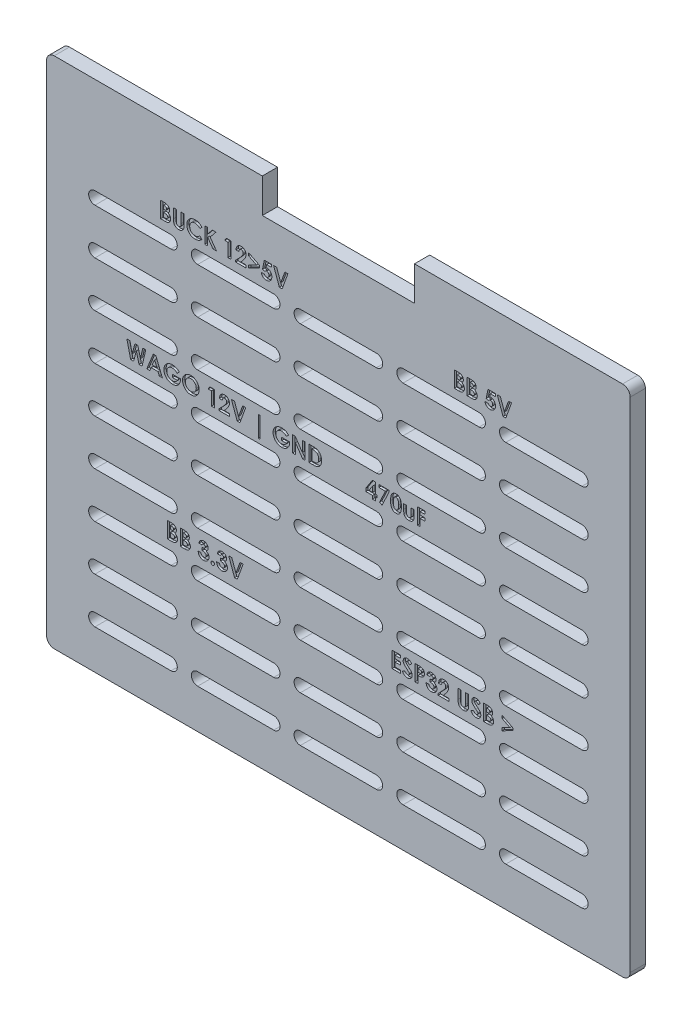
SolidWorks part; units mm, degrees
ref_plane "Front Plane" through (0, 0, 0) normal (0, 0, 1) x (1, 0, 0)
ref_plane "Top Plane" through (0, 0, 0) normal (0, 1, 0) x (1, 0, 0)
ref_plane "Right Plane" through (0, 0, 0) normal (1, 0, 0) x (0, 0, -1)
ref_plane "P1_Front_14" through (0, 0, 14) normal (0, 0, 1) x (1, 0, 0)
sketch "Sketch1" plane through (0, 0, 14) normal (0, 0, 1) x (1, 0, 0)
  line L0 (-74.7, 9) -> (74.7, 9)
  line L1 (76.7, 11) -> (76.7, 142)
  line L2 (74.7, 144) -> (-74.7, 144)
  line L3 (-76.7, 142) -> (-76.7, 11)
  arc A0 (-76.7, 11) -> (-74.7, 9) centre (-74.7, 11) ccw
  arc A1 (74.7, 9) -> (76.7, 11) centre (74.7, 11) ccw
  arc A2 (76.7, 142) -> (74.7, 144) centre (74.7, 142) ccw
  arc A3 (-74.7, 144) -> (-76.7, 142) centre (-74.7, 142) ccw
extrude "Plate" add sketch "Sketch1" along normal blind 4
sketch "Sketch2" plane through (0, 0, 14) normal (0, 0, 1) x (1, 0, 0)
  line L0 (-64, 21) -> (-44, 21) construction
  line L1 (-20, 135) -> (20, 135)
  line L2 (-20, 135) -> (-20, 144)
  line L3 (-20, 144) -> (20, 144)
  line L4 (20, 135) -> (20, 144)
  line L5 (-20, 135) -> (20, 144) construction
  line L6 (-20, 144) -> (20, 135) construction
  line L7 (-64, 22.65) -> (-44, 22.65)
  line L8 (-64, 19.35) -> (-44, 19.35)
  line L9 (-37, 21) -> (-17, 21) construction
  line L10 (-37, 22.65) -> (-17, 22.65)
  line L11 (-37, 19.35) -> (-17, 19.35)
  line L12 (-10, 21) -> (10, 21) construction
  line L13 (-10, 22.65) -> (10, 22.65)
  line L14 (-10, 19.35) -> (10, 19.35)
  line L15 (17, 21) -> (37, 21) construction
  line L16 (17, 22.65) -> (37, 22.65)
  line L17 (17, 19.35) -> (37, 19.35)
  line L18 (44, 21) -> (64, 21) construction
  line L19 (44, 22.65) -> (64, 22.65)
  line L20 (44, 19.35) -> (64, 19.35)
  line L21 (-64, 33) -> (-44, 33) construction
  line L22 (-64, 34.65) -> (-44, 34.65)
  line L23 (-64, 31.35) -> (-44, 31.35)
  line L24 (-37, 33) -> (-17, 33) construction
  line L25 (-37, 34.65) -> (-17, 34.65)
  line L26 (-37, 31.35) -> (-17, 31.35)
  line L27 (-10, 33) -> (10, 33) construction
  line L28 (-10, 34.65) -> (10, 34.65)
  line L29 (-10, 31.35) -> (10, 31.35)
  line L30 (17, 33) -> (37, 33) construction
  line L31 (17, 34.65) -> (37, 34.65)
  line L32 (17, 31.35) -> (37, 31.35)
  line L33 (44, 33) -> (64, 33) construction
  line L34 (44, 34.65) -> (64, 34.65)
  line L35 (44, 31.35) -> (64, 31.35)
  line L36 (-64, 45) -> (-44, 45) construction
  line L37 (-64, 46.65) -> (-44, 46.65)
  line L38 (-64, 43.35) -> (-44, 43.35)
  line L39 (-37, 45) -> (-17, 45) construction
  line L40 (-37, 46.65) -> (-17, 46.65)
  line L41 (-37, 43.35) -> (-17, 43.35)
  line L42 (-10, 45) -> (10, 45) construction
  line L43 (-10, 46.65) -> (10, 46.65)
  line L44 (-10, 43.35) -> (10, 43.35)
  line L45 (17, 45) -> (37, 45) construction
  line L46 (17, 46.65) -> (37, 46.65)
  line L47 (17, 43.35) -> (37, 43.35)
  line L48 (44, 45) -> (64, 45) construction
  line L49 (44, 46.65) -> (64, 46.65)
  line L50 (44, 43.35) -> (64, 43.35)
  line L51 (-64, 57) -> (-44, 57) construction
  line L52 (-64, 58.65) -> (-44, 58.65)
  line L53 (-64, 55.35) -> (-44, 55.35)
  line L54 (-37, 57) -> (-17, 57) construction
  line L55 (-37, 58.65) -> (-17, 58.65)
  line L56 (-37, 55.35) -> (-17, 55.35)
  line L57 (-10, 57) -> (10, 57) construction
  line L58 (-10, 58.65) -> (10, 58.65)
  line L59 (-10, 55.35) -> (10, 55.35)
  line L60 (17, 57) -> (37, 57) construction
  line L61 (17, 58.65) -> (37, 58.65)
  line L62 (17, 55.35) -> (37, 55.35)
  line L63 (44, 57) -> (64, 57) construction
  line L64 (44, 58.65) -> (64, 58.65)
  line L65 (44, 55.35) -> (64, 55.35)
  line L66 (-64, 69) -> (-44, 69) construction
  line L67 (-64, 70.65) -> (-44, 70.65)
  line L68 (-64, 67.35) -> (-44, 67.35)
  line L69 (-37, 69) -> (-17, 69) construction
  line L70 (-37, 70.65) -> (-17, 70.65)
  line L71 (-37, 67.35) -> (-17, 67.35)
  line L72 (-10, 69) -> (10, 69) construction
  line L73 (-10, 70.65) -> (10, 70.65)
  line L74 (-10, 67.35) -> (10, 67.35)
  line L75 (17, 69) -> (37, 69) construction
  line L76 (17, 70.65) -> (37, 70.65)
  line L77 (17, 67.35) -> (37, 67.35)
  line L78 (44, 69) -> (64, 69) construction
  line L79 (44, 70.65) -> (64, 70.65)
  line L80 (44, 67.35) -> (64, 67.35)
  line L81 (-64, 81) -> (-44, 81) construction
  line L82 (-64, 82.65) -> (-44, 82.65)
  line L83 (-64, 79.35) -> (-44, 79.35)
  line L84 (-37, 81) -> (-17, 81) construction
  line L85 (-37, 82.65) -> (-17, 82.65)
  line L86 (-37, 79.35) -> (-17, 79.35)
  line L87 (-10, 81) -> (10, 81) construction
  line L88 (-10, 82.65) -> (10, 82.65)
  line L89 (-10, 79.35) -> (10, 79.35)
  line L90 (17, 81) -> (37, 81) construction
  line L91 (17, 82.65) -> (37, 82.65)
  line L92 (17, 79.35) -> (37, 79.35)
  line L93 (44, 81) -> (64, 81) construction
  line L94 (44, 82.65) -> (64, 82.65)
  line L95 (44, 79.35) -> (64, 79.35)
  line L96 (-64, 93) -> (-44, 93) construction
  line L97 (-64, 94.65) -> (-44, 94.65)
  line L98 (-64, 91.35) -> (-44, 91.35)
  line L99 (-37, 93) -> (-17, 93) construction
  line L100 (-37, 94.65) -> (-17, 94.65)
  line L101 (-37, 91.35) -> (-17, 91.35)
  line L102 (-10, 93) -> (10, 93) construction
  line L103 (-10, 94.65) -> (10, 94.65)
  line L104 (-10, 91.35) -> (10, 91.35)
  line L105 (17, 93) -> (37, 93) construction
  line L106 (17, 94.65) -> (37, 94.65)
  line L107 (17, 91.35) -> (37, 91.35)
  line L108 (44, 93) -> (64, 93) construction
  line L109 (44, 94.65) -> (64, 94.65)
  line L110 (44, 91.35) -> (64, 91.35)
  line L111 (-64, 105) -> (-44, 105) construction
  line L112 (-64, 106.65) -> (-44, 106.65)
  line L113 (-64, 103.35) -> (-44, 103.35)
  line L114 (-37, 105) -> (-17, 105) construction
  line L115 (-37, 106.65) -> (-17, 106.65)
  line L116 (-37, 103.35) -> (-17, 103.35)
  line L117 (-10, 105) -> (10, 105) construction
  line L118 (-10, 106.65) -> (10, 106.65)
  line L119 (-10, 103.35) -> (10, 103.35)
  line L120 (17, 105) -> (37, 105) construction
  line L121 (17, 106.65) -> (37, 106.65)
  line L122 (17, 103.35) -> (37, 103.35)
  line L123 (44, 105) -> (64, 105) construction
  line L124 (44, 106.65) -> (64, 106.65)
  line L125 (44, 103.35) -> (64, 103.35)
  line L126 (-64, 117) -> (-44, 117) construction
  line L127 (-64, 118.65) -> (-44, 118.65)
  line L128 (-64, 115.35) -> (-44, 115.35)
  line L129 (-37, 117) -> (-17, 117) construction
  line L130 (-37, 118.65) -> (-17, 118.65)
  line L131 (-37, 115.35) -> (-17, 115.35)
  line L132 (-10, 117) -> (10, 117) construction
  line L133 (-10, 118.65) -> (10, 118.65)
  line L134 (-10, 115.35) -> (10, 115.35)
  line L135 (17, 117) -> (37, 117) construction
  line L136 (17, 118.65) -> (37, 118.65)
  line L137 (17, 115.35) -> (37, 115.35)
  line L138 (44, 117) -> (64, 117) construction
  line L139 (44, 118.65) -> (64, 118.65)
  line L140 (44, 115.35) -> (64, 115.35)
  arc A0 (-64, 22.65) -> (-64, 19.35) centre (-64, 21) ccw
  arc A1 (-44, 19.35) -> (-44, 22.65) centre (-44, 21) ccw
  arc A2 (-37, 22.65) -> (-37, 19.35) centre (-37, 21) ccw
  arc A3 (-17, 19.35) -> (-17, 22.65) centre (-17, 21) ccw
  arc A4 (-10, 22.65) -> (-10, 19.35) centre (-10, 21) ccw
  arc A5 (10, 19.35) -> (10, 22.65) centre (10, 21) ccw
  arc A6 (17, 22.65) -> (17, 19.35) centre (17, 21) ccw
  arc A7 (37, 19.35) -> (37, 22.65) centre (37, 21) ccw
  arc A8 (44, 22.65) -> (44, 19.35) centre (44, 21) ccw
  arc A9 (64, 19.35) -> (64, 22.65) centre (64, 21) ccw
  arc A10 (-64, 34.65) -> (-64, 31.35) centre (-64, 33) ccw
  arc A11 (-44, 31.35) -> (-44, 34.65) centre (-44, 33) ccw
  arc A12 (-37, 34.65) -> (-37, 31.35) centre (-37, 33) ccw
  arc A13 (-17, 31.35) -> (-17, 34.65) centre (-17, 33) ccw
  arc A14 (-10, 34.65) -> (-10, 31.35) centre (-10, 33) ccw
  arc A15 (10, 31.35) -> (10, 34.65) centre (10, 33) ccw
  arc A16 (17, 34.65) -> (17, 31.35) centre (17, 33) ccw
  arc A17 (37, 31.35) -> (37, 34.65) centre (37, 33) ccw
  arc A18 (44, 34.65) -> (44, 31.35) centre (44, 33) ccw
  arc A19 (64, 31.35) -> (64, 34.65) centre (64, 33) ccw
  arc A20 (-64, 46.65) -> (-64, 43.35) centre (-64, 45) ccw
  arc A21 (-44, 43.35) -> (-44, 46.65) centre (-44, 45) ccw
  arc A22 (-37, 46.65) -> (-37, 43.35) centre (-37, 45) ccw
  arc A23 (-17, 43.35) -> (-17, 46.65) centre (-17, 45) ccw
  arc A24 (-10, 46.65) -> (-10, 43.35) centre (-10, 45) ccw
  arc A25 (10, 43.35) -> (10, 46.65) centre (10, 45) ccw
  arc A26 (17, 46.65) -> (17, 43.35) centre (17, 45) ccw
  arc A27 (37, 43.35) -> (37, 46.65) centre (37, 45) ccw
  arc A28 (44, 46.65) -> (44, 43.35) centre (44, 45) ccw
  arc A29 (64, 43.35) -> (64, 46.65) centre (64, 45) ccw
  arc A30 (-64, 58.65) -> (-64, 55.35) centre (-64, 57) ccw
  arc A31 (-44, 55.35) -> (-44, 58.65) centre (-44, 57) ccw
  arc A32 (-37, 58.65) -> (-37, 55.35) centre (-37, 57) ccw
  arc A33 (-17, 55.35) -> (-17, 58.65) centre (-17, 57) ccw
  arc A34 (-10, 58.65) -> (-10, 55.35) centre (-10, 57) ccw
  arc A35 (10, 55.35) -> (10, 58.65) centre (10, 57) ccw
  arc A36 (17, 58.65) -> (17, 55.35) centre (17, 57) ccw
  arc A37 (37, 55.35) -> (37, 58.65) centre (37, 57) ccw
  arc A38 (44, 58.65) -> (44, 55.35) centre (44, 57) ccw
  arc A39 (64, 55.35) -> (64, 58.65) centre (64, 57) ccw
  arc A40 (-64, 70.65) -> (-64, 67.35) centre (-64, 69) ccw
  arc A41 (-44, 67.35) -> (-44, 70.65) centre (-44, 69) ccw
  arc A42 (-37, 70.65) -> (-37, 67.35) centre (-37, 69) ccw
  arc A43 (-17, 67.35) -> (-17, 70.65) centre (-17, 69) ccw
  arc A44 (-10, 70.65) -> (-10, 67.35) centre (-10, 69) ccw
  arc A45 (10, 67.35) -> (10, 70.65) centre (10, 69) ccw
  arc A46 (17, 70.65) -> (17, 67.35) centre (17, 69) ccw
  arc A47 (37, 67.35) -> (37, 70.65) centre (37, 69) ccw
  arc A48 (44, 70.65) -> (44, 67.35) centre (44, 69) ccw
  arc A49 (64, 67.35) -> (64, 70.65) centre (64, 69) ccw
  arc A50 (-64, 82.65) -> (-64, 79.35) centre (-64, 81) ccw
  arc A51 (-44, 79.35) -> (-44, 82.65) centre (-44, 81) ccw
  arc A52 (-37, 82.65) -> (-37, 79.35) centre (-37, 81) ccw
  arc A53 (-17, 79.35) -> (-17, 82.65) centre (-17, 81) ccw
  arc A54 (-10, 82.65) -> (-10, 79.35) centre (-10, 81) ccw
  arc A55 (10, 79.35) -> (10, 82.65) centre (10, 81) ccw
  arc A56 (17, 82.65) -> (17, 79.35) centre (17, 81) ccw
  arc A57 (37, 79.35) -> (37, 82.65) centre (37, 81) ccw
  arc A58 (44, 82.65) -> (44, 79.35) centre (44, 81) ccw
  arc A59 (64, 79.35) -> (64, 82.65) centre (64, 81) ccw
  arc A60 (-64, 94.65) -> (-64, 91.35) centre (-64, 93) ccw
  arc A61 (-44, 91.35) -> (-44, 94.65) centre (-44, 93) ccw
  arc A62 (-37, 94.65) -> (-37, 91.35) centre (-37, 93) ccw
  arc A63 (-17, 91.35) -> (-17, 94.65) centre (-17, 93) ccw
  arc A64 (-10, 94.65) -> (-10, 91.35) centre (-10, 93) ccw
  arc A65 (10, 91.35) -> (10, 94.65) centre (10, 93) ccw
  arc A66 (17, 94.65) -> (17, 91.35) centre (17, 93) ccw
  arc A67 (37, 91.35) -> (37, 94.65) centre (37, 93) ccw
  arc A68 (44, 94.65) -> (44, 91.35) centre (44, 93) ccw
  arc A69 (64, 91.35) -> (64, 94.65) centre (64, 93) ccw
  arc A70 (-64, 106.65) -> (-64, 103.35) centre (-64, 105) ccw
  arc A71 (-44, 103.35) -> (-44, 106.65) centre (-44, 105) ccw
  arc A72 (-37, 106.65) -> (-37, 103.35) centre (-37, 105) ccw
  arc A73 (-17, 103.35) -> (-17, 106.65) centre (-17, 105) ccw
  arc A74 (-10, 106.65) -> (-10, 103.35) centre (-10, 105) ccw
  arc A75 (10, 103.35) -> (10, 106.65) centre (10, 105) ccw
  arc A76 (17, 106.65) -> (17, 103.35) centre (17, 105) ccw
  arc A77 (37, 103.35) -> (37, 106.65) centre (37, 105) ccw
  arc A78 (44, 106.65) -> (44, 103.35) centre (44, 105) ccw
  arc A79 (64, 103.35) -> (64, 106.65) centre (64, 105) ccw
  arc A80 (-64, 118.65) -> (-64, 115.35) centre (-64, 117) ccw
  arc A81 (-44, 115.35) -> (-44, 118.65) centre (-44, 117) ccw
  arc A82 (-37, 118.65) -> (-37, 115.35) centre (-37, 117) ccw
  arc A83 (-17, 115.35) -> (-17, 118.65) centre (-17, 117) ccw
  arc A84 (-10, 118.65) -> (-10, 115.35) centre (-10, 117) ccw
  arc A85 (10, 115.35) -> (10, 118.65) centre (10, 117) ccw
  arc A86 (17, 118.65) -> (17, 115.35) centre (17, 117) ccw
  arc A87 (37, 115.35) -> (37, 118.65) centre (37, 117) ccw
  arc A88 (44, 118.65) -> (44, 115.35) centre (44, 117) ccw
  arc A89 (64, 115.35) -> (64, 118.65) centre (64, 117) ccw
  point P0 (0, 139.5)
  point P7 (-54, 21)
  point P12 (-27, 21)
  point P19 (0, 21)
  point P26 (27, 21)
  point P33 (54, 21)
  point P40 (-54, 33)
  point P47 (-27, 33)
  point P54 (0, 33)
  point P61 (27, 33)
  point P68 (54, 33)
  point P75 (-54, 45)
  point P82 (-27, 45)
  point P89 (0, 45)
  point P96 (27, 45)
  point P103 (54, 45)
  point P110 (-54, 57)
  point P117 (-27, 57)
  point P124 (0, 57)
  point P131 (27, 57)
  point P138 (54, 57)
  point P145 (-54, 69)
  point P152 (-27, 69)
  point P159 (0, 69)
  point P166 (27, 69)
  point P173 (54, 69)
  point P180 (-54, 81)
  point P187 (-27, 81)
  point P194 (0, 81)
  point P201 (27, 81)
  point P208 (54, 81)
  point P215 (-54, 93)
  point P222 (-27, 93)
  point P229 (0, 93)
  point P236 (27, 93)
  point P243 (54, 93)
  point P250 (-54, 105)
  point P257 (-27, 105)
  point P264 (0, 105)
  point P271 (27, 105)
  point P278 (54, 105)
  point P285 (-54, 117)
  point P292 (-27, 117)
  point P299 (0, 117)
  point P306 (27, 117)
  point P313 (54, 117)
  point P320 (0, 0)
extrude "Notch and mounting slots" cut sketch "Sketch2" along normal through all
ref_plane "P2_Front_18" through (0, 0, 18) normal (0, 0, 1) x (1, 0, 0)
sketch "Sketch3" plane through (0, 0, 18) normal (0, 0, 1) x (1, 0, 0)
  text T0 "BUCK 12>5V" font "Century Gothic" height 4.2
  text T1 "BB 5V" font "Century Gothic" height 4.2
  text T2 "WAGO 12V | GND" font "Century Gothic" height 4.2
  text T3 "470uF" font "Century Gothic" height 4.2
  text T4 "BB 3.3V" font "Century Gothic" height 4.2
  text T5 "ESP32 USB >" font "Century Gothic" height 4.2
extrude "Zone labels" cut sketch "Sketch3" against normal blind 0.6
